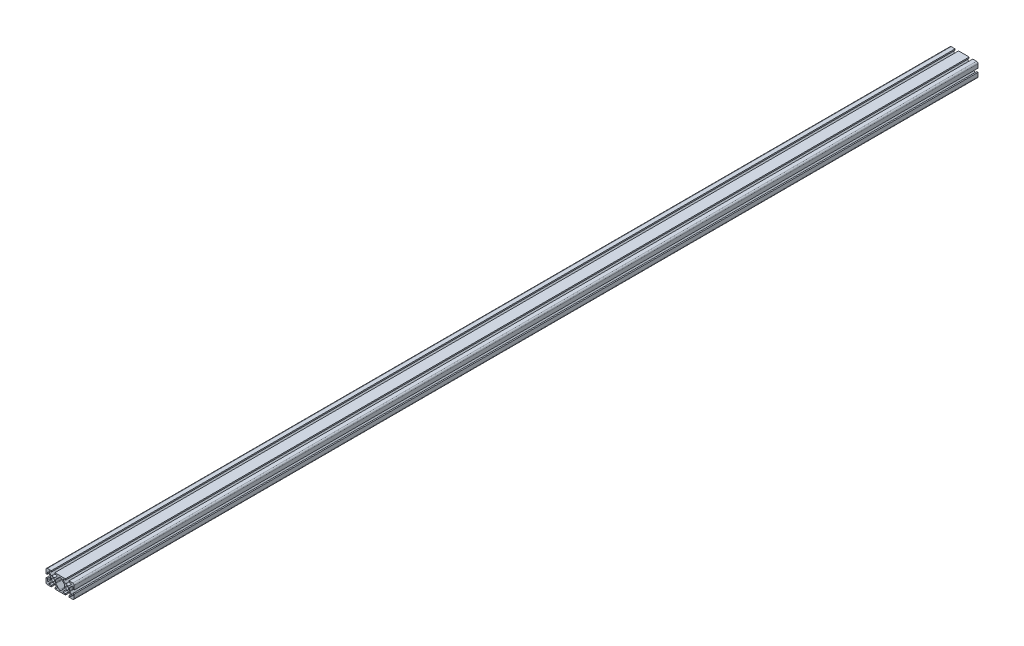
SolidWorks part; units mm, degrees
ref_plane "Front Plane" through (0, 0, 0) normal (0, 0, 1) x (1, 0, 0)
ref_plane "Top Plane" through (0, 0, 0) normal (0, 1, 0) x (1, 0, 0)
ref_plane "Right Plane" through (0, 0, 0) normal (1, 0, 0) x (0, 0, -1)
sketch "Sketch1" plane through (0, 0, 0) normal (0, 0, 1) x (1, 0, 0)
  line L0 (10, 10) -> (10, -10) construction
  line L1 (-20, 0) -> (20, 0) construction
  line L2 (12.5, -10) -> (20, -10)
  line L3 (20, -10) -> (20, -2.5)
  line L4 (12.5, -10) -> (12.5, -8.2134)
  line L5 (12.5, -8.2134) -> (16.95, -8.2134)
  line L6 (16.95, -8.2134) -> (12.3366, -3.6)
  line L7 (10, 0) -> (20, -10) construction
  line L8 (20, -2.5) -> (18.2134, -2.5)
  line L9 (18.2134, -2.5) -> (18.2134, -6.95)
  line L10 (18.2134, -6.95) -> (13.6, -2.3366)
  line L11 (15.9067, -4.6433) -> (14.6433, -5.9067) construction
  line L12 (0, 10) -> (0, -10) construction
  line L13 (0, -10) -> (-20, -10) construction
  line L14 (-10, 10) -> (10, 10) construction
  line L15 (20, 2.5) -> (20, -2.5) construction
  circle A0 centre (10, 0) radius 2.15
  arc A1 (15.5015, -8.2134) -> (15.9257, -7.1891) centre (15.5015, -7.6134) ccw construction
  point P8 (10, -3.6)
  point P16 (15.275, -5.275)
  point P30 (20, 0)
  dimension "Center Hole Diameter" = 4.3
  dimension "D3" = 0.6
  dimension "Rail Width" = 20
  dimension "T-Slot Width" = 5
  dimension "Slot Depth" = 6.4
  dimension "Rail Height" = 40
  dimension "Inner Slot Width" = 13.9
  dimension "Hole Spacing" = 20
sketch "Sketch2" plane through (0, 0, 0) normal (1, 0, 0) x (0, 0, -1)
  line L0 (-640, -10) -> (640, -10) construction
  line L1 (-600, 0) -> (600, 0) construction
  point P6 (-600, 0)
  point P8 (600, 0)
  dimension "Length" = 1280
  dimension "D1" = 40
sketch "Sketch3" plane through (0, 0, 0) normal (0, 0, 1) x (1, 0, 0)
  line L0 (12.5, -10) -> (17.9, -10)
  line L1 (12.5, -10) -> (20, -10) construction
  line L2 (12.5, -10) -> (12.5, -8.2134) construction
  line L3 (12.5, -8.2134) -> (16.95, -8.2134) construction
  line L4 (12.5, -8.2134) -> (12.5, -10)
  line L5 (12.5, -8.2134) -> (16.95, -8.2134)
  line L6 (10, -3.6) -> (12.3366, -3.6)
  line L7 (16.95, -8.2134) -> (12.3366, -3.6) construction
  line L8 (12.3366, -3.6) -> (16.95, -8.2134)
  line L9 (20, -10) -> (20, -2.5) construction
  line L10 (18.2134, -6.95) -> (13.6, -2.3366) construction
  line L11 (18.2134, -2.5) -> (18.2134, -6.95) construction
  line L12 (18.2134, -6.95) -> (18.2134, -2.5)
  line L13 (20, -2.5) -> (18.2134, -2.5) construction
  line L14 (18.2134, -2.5) -> (20, -2.5)
  line L15 (20, -2.5) -> (20, -7.9)
  line L16 (18.2134, -6.95) -> (13.6, -2.3366)
  line L17 (13.6, 0) -> (13.6, -2.3366)
  line L18 (-20, 0) -> (20, 0) construction
  line L19 (10, -3.6) -> (10, -2.15)
  line L20 (10, 10) -> (10, -10) construction
  line L21 (13.6, 0) -> (12.15, 0)
  arc A5 (17.9, -10) -> (20, -7.9) centre (17.9, -7.9) ccw
  circle A10 centre (10, 0) radius 2.15 construction
  arc A11 (10, -2.15) -> (12.15, 0) centre (10, 0) ccw
  dimension "D1" = 2.1
extrude "Boss-Extrude1" add sketch "Sketch3" along normal mid plane 1280
sketch "Sketch4" plane through (0, 0, 0) normal (0, 0, 1) x (1, 0, 0)
  line L0 (10, -3.6) -> (7.6634, -3.6)
  line L4 (7.6634, -3.6) -> (3.05, -8.2134)
  line L5 (3.05, -8.2134) -> (7.5, -8.2134)
  line L6 (7.5, -8.2134) -> (7.5, -10)
  line L18 (7.5, -10) -> (0, -10)
  line L19 (12.5, -10) -> (12.5, -8.2134) construction
  line L20 (12.5, -8.2134) -> (16.95, -8.2134) construction
  line L21 (10, -3.6) -> (12.3366, -3.6) construction
  line L22 (16.95, -8.2134) -> (12.3366, -3.6) construction
  line L23 (0, -8.7366) -> (6.4, -2.3366)
  line L24 (0, 10) -> (0, -10) construction
  line L25 (6.4, -2.3366) -> (6.4, 0)
  line L26 (-20, 0) -> (20, 0) construction
  line L27 (6.4, 0) -> (7.85, 0)
  line L28 (13.6, 0) -> (12.15, 0) construction
  line L29 (0, -8.7366) -> (0, -10)
  line L30 (10, -2.15) -> (10, -3.6)
  circle A4 centre (10, 0) radius 2.15 construction
  arc A5 (7.85, 0) -> (10, -2.15) centre (10, 0) ccw
extrude "Boss-Extrude2" add sketch "Sketch4" along normal mid plane 1280
mirror "Mirror1" about plane through (0, 0, 0) normal (1, 0, 0) of bodies 137 134
mirror "Mirror2" about plane through (0, 0, 0) normal (0, 1, 0) of bodies 135
fillet "Fillet1" radius 0.75 24 edges at (-7.6634, -3.6, 0) (-12.3366, -3.6, 0) (12.3366, -3.6, 0) (7.6634, -3.6, 0) (-3.05, -8.2134, 0) (-18.2134, -6.95, 0) (-16.95, -8.2134, 0) (-13.6, -2.3366, 0) (-18.2134, 6.95, 0) (-16.95, 8.2134, 0) (-12.3366, 3.6, 0) (-7.6634, 3.6, 0) (-13.6, 2.3366, 0) (-3.05, 8.2134, 0) (3.05, 8.2134, 0) (13.6, -2.3366, 0) (13.6, 2.3366, 0) (7.6634, 3.6, 0) (12.3366, 3.6, 0) (18.2134, 6.95, 0) (16.95, 8.2134, 0) (18.2134, -6.95, 0) (16.95, -8.2134, 0) (3.05, -8.2134, 0)
fillet "Fillet2" radius 1.25 6 edges at (0, -8.7366, 0) (-6.4, -2.3366, 0) (-6.4, 2.3366, 0) (6.4, -2.3366, 0) (6.4, 2.3366, 0) (0, 8.7366, 0)
equation "\"D1@Sketch3\" = \"D3@Sketch1\" * 3.5"
equation "\"D1@Boss-Extrude1\" = \"Length@Sketch2\""
equation "\"D1@Boss-Extrude2\" = \"Length@Sketch2\""
equation "\"D1@Sketch2\"=\"Rail Height@Sketch1\""
